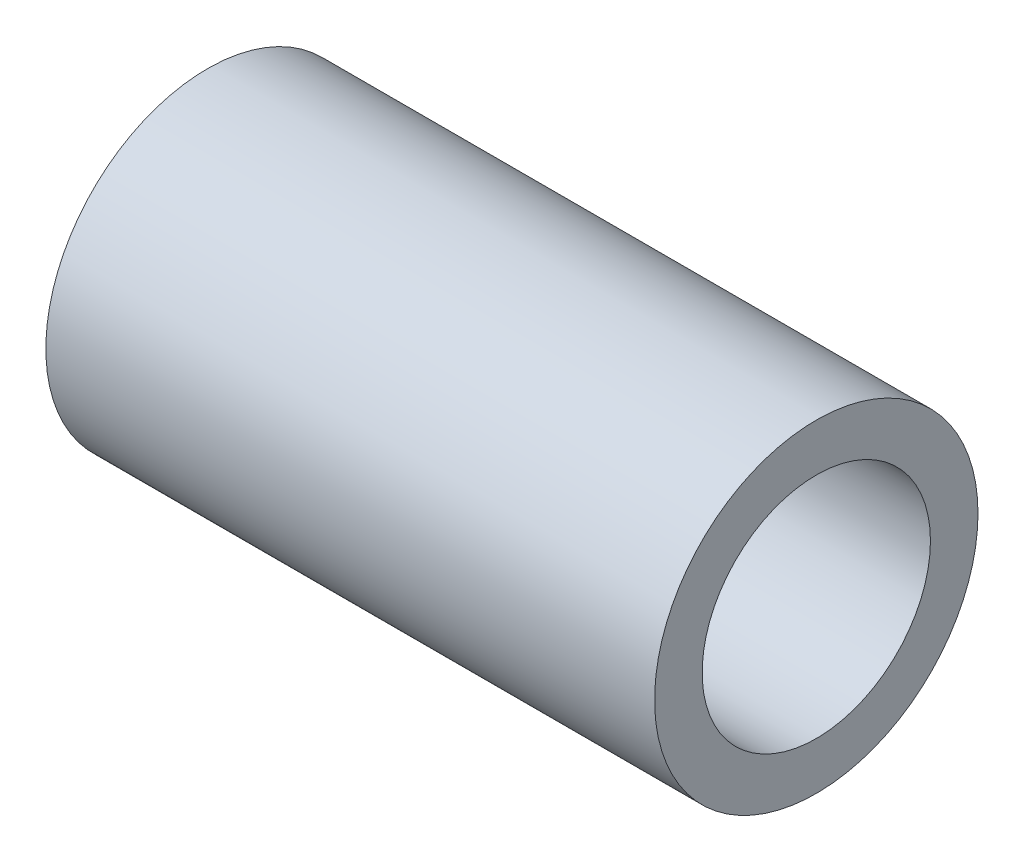
SolidWorks part; units mm, degrees
note: The reader was unsure of these and kept them because the rebuilt part matched: shared geometry of "Sketch1<3>".
material "Silicon Rubber"
ref_plane "X-Y Datum" through (0, 0, 0) normal (0, 0, 1) x (1, 0, 0)
ref_plane "X-Z Datum" through (0, 0, 0) normal (0, 1, 0) x (1, 0, 0)
ref_plane "Y-Z Datum" through (0, 0, 0) normal (1, 0, 0) x (0, 0, -1)
sketch "Sketch1" plane through (0, 0, 0) normal (0, 0, 1) x (1, 0, 0)
  line L0 (0, 0) -> (50.8, 0)
  line L1 (55.1739, 0) -> (-55.1739, 0) construction
sweep "Sweep1" add path "Sketch1" circular profile diameter 26.9875 parameters "D3"=26.9875
sweep "Cut-Sweep1" cut path "Sketch1<3>" circular profile diameter 19.05 parameters "D3"=19.05
sketch "Sketch1<3>" plane through (0, 0, 0) normal (0, 0, 1) x (1, 0, 0) same geometry as "Sketch1"
